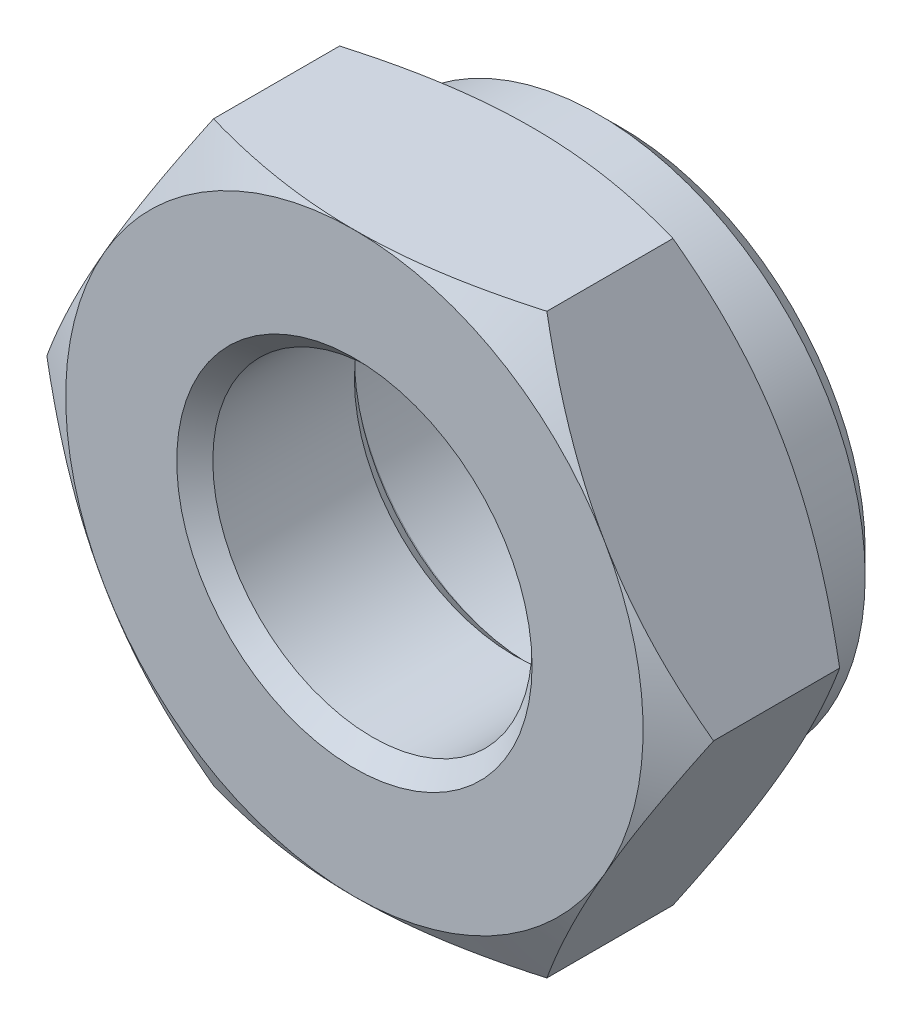
SolidWorks part; units mm, degrees
ref_plane "Front Plane" through (0, 0, 0) normal (0, 0, 1) x (1, 0, 0)
ref_plane "Top Plane" through (0, 0, 0) normal (0, 1, 0) x (1, 0, 0)
ref_plane "Right Plane" through (0, 0, 0) normal (1, 0, 0) x (0, 0, -1)
sketch "Sketch1" plane through (0, 0, 0) normal (1, 0, 0) x (0, 0, -1)
  line L0 (-6, 0) -> (-6, 6.5)
  line L1 (-6, 6.5) -> (-5.2494, 7.8)
  line L2 (-5.2494, 7.8) -> (-2.7506, 7.8)
  line L3 (-2.7506, 7.8) -> (-2, 6.5)
  line L4 (-2, 6.5) -> (-2, 6)
  line L5 (-2, 6) -> (-0.5, 6)
  line L6 (-0.5, 6) -> (0, 5.5)
  line L7 (0, 5.5) -> (0, 0)
  line L8 (0, 0) -> (-6, 0)
  line L9 (0, 0) -> (-6, 0) construction
revolve "Revolve1" add sketch "Sketch1" angle 360 about L9 reverse direction yes
sketch "Sketch2" plane through (0, 0, 0) normal (1, 0, 0) x (0, 0, -1)
  line L0 (-6, 0) -> (-6, 4)
  line L1 (-6, 4) -> (-5.594, 3.594)
  line L2 (-5.594, 3.594) -> (-2.406, 3.594)
  line L3 (-2.406, 3.594) -> (-2, 4)
  line L4 (-2, 4) -> (-2, 4.05)
  line L5 (-1.8, 4.25) -> (0, 4.25)
  line L6 (0, 4.25) -> (0, 0)
  line L7 (0, 0) -> (-6, 0)
  line L8 (0, 0) -> (-6, 0) construction
  arc A0 (-2, 4.05) -> (-1.8, 4.25) centre (-1.8, 4.05) cw
revolve "Cut-Revolve1" cut sketch "Sketch2" angle 360 about L8 reverse direction yes
cosmetic thread "Cosmetic Thread1" parameters "D1"=4, "D2"=8
sketch "Sketch3" plane through (0, 0, 0) normal (0, 0, 1) x (1, 0, 0)
  line L0 (-13, -13) -> (13, -13)
  line L1 (13, -13) -> (13, 13)
  line L2 (13, 13) -> (-13, 13)
  line L3 (-13, 13) -> (-13, -13)
  line L4 (-7.5056, 0) -> (-3.7528, -6.5)
  line L5 (-3.7528, -6.5) -> (3.7528, -6.5)
  line L6 (3.7528, -6.5) -> (7.5056, 0)
  line L7 (7.5056, 0) -> (3.7528, 6.5)
  line L8 (3.7528, 6.5) -> (-3.7528, 6.5)
  line L9 (-3.7528, 6.5) -> (-7.5056, 0)
extrude "Cut-Extrude1" cut sketch "Sketch3" along normal blind 6
ref_plane "ANBAU XY" through (0, 0, 0) normal (0, 0, 1) x (1, 0, 0)
ref_plane "ANBAU XZ" through (0, 0, 0) normal (0, -1, 0) x (-1, 0, 0)
ref_plane "ANBAU YZ" through (0, 0, 0) normal (1, 0, 0) x (0, 0, -1)
ref_axis "ANBAU X" through (-80.9, 0, 0) along (1, 0, 0)
ref_axis "ANBAU Y" through (0, -50, 0) along (0, 1, 0)
ref_axis "ANBAU Z" through (0, 0, 80.9) along (0, 0, -1)
sketch3d "ANBAU"
  point P0 (0, 0, 0)
other "Freeze***"
